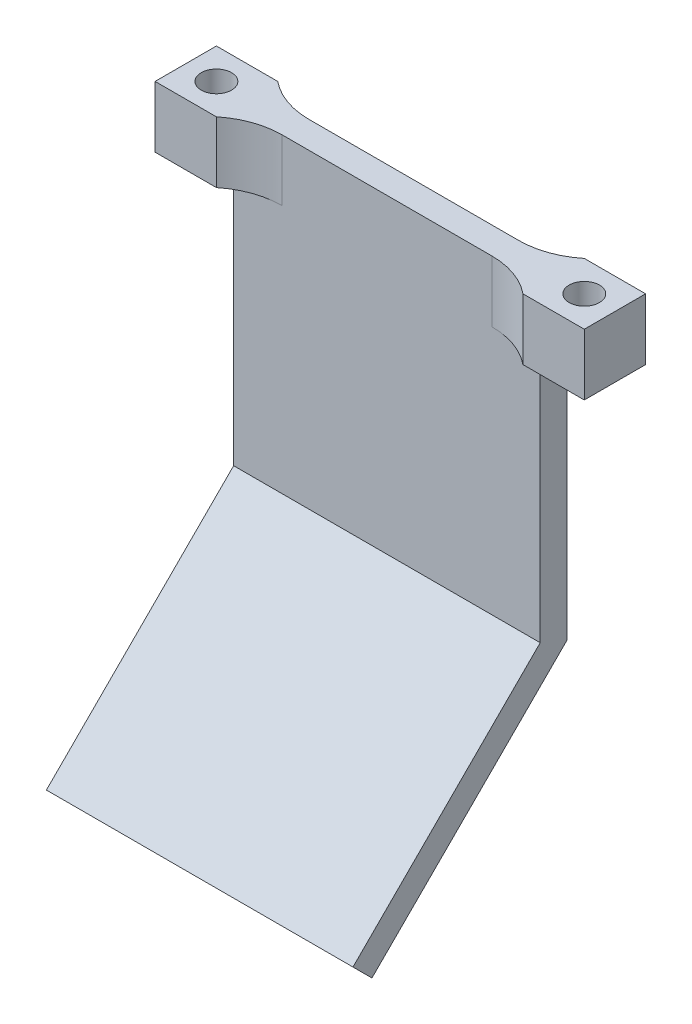
SolidWorks part; units mm, degrees
ref_plane "前视基准面" through (0, 0, 0) normal (0, 0, 1) x (1, 0, 0)
ref_plane "上视基准面" through (0, 0, 0) normal (0, 1, 0) x (1, 0, 0)
ref_plane "右视基准面" through (0, 0, 0) normal (1, 0, 0) x (0, 0, -1)
other "Configuration Table"
sketch "草图2" plane through (0, 0, 0) normal (1, 0, 0) x (0, 0, -1)
  line L0 (0, 0) -> (0, -42)
  line L1 (0, -42) -> (-25.4558, -67.4558)
  line L2 (-3.5, 0) -> (-3.5, -40.5503)
  line L3 (-3.5, -40.5503) -> (-27.9307, -64.981)
  line L4 (-3.5, 0) -> (0, 0)
  line L5 (-27.9307, -64.981) -> (-25.4558, -67.4558)
  point P3 (-3.5, -40.5503)
  dimension "D1" = 3.5
extrude "凸台-拉伸1" add sketch "草图2" along normal blind 40
sketch "草图3" plane through (0, 0, 3.5) normal (0, 0, 1) x (1, 0, 0)
  line L0 (40, -20.2751) -> (0, -20.2751)
  line L1 (40, 0) -> (40, -40.5503) construction
  line L2 (0, 0) -> (0, -40.5503) construction
  line L3 (20, -20.2751) -> (20, -4.2751)
  circle A0 centre (16, -4.2751) radius 1.5
  circle A1 centre (24, -4.2751) radius 1.5
  circle A2 centre (24, -36.2751) radius 1.5
  circle A3 centre (16, -36.2751) radius 1.5
sketch "草图4" plane through (0, 0, 0) normal (-1, 0, 0) x (0, 0, 1)
  line L5 (-2.25, 0) -> (5.75, 0)
  line L6 (-2.25, 0) -> (-2.25, -8)
  line L7 (-2.25, -8) -> (5.75, -8)
  line L8 (5.75, 0) -> (5.75, -8)
extrude "凸台-拉伸2" add sketch "草图4" along normal blind 8
sketch "草图5" plane through (0, 0, 0) normal (0, 1, 0) x (1, 0, 0)
  circle A0 centre (-4, -1.75) radius 1.98
extrude "切除-拉伸2" cut sketch "草图5" against normal blind 8
fillet "圆角1" radius 10 1 edges at (0, -4, 0)
fillet "圆角2" radius 10 1 edges at (0, -4, 3.5)
sketch "草图6" plane through (40, 0, 0) normal (1, 0, 0) x (0, 0, -1)
  line L1 (-5.75, 0) -> (2.25, 0)
  line L2 (-5.75, 0) -> (-5.75, -8)
  line L3 (-5.75, -8) -> (2.25, -8)
  line L4 (2.25, 0) -> (2.25, -8)
extrude "凸台-拉伸3" add sketch "草图6" along normal blind 8
sketch "草图7" plane through (0, 0, 0) normal (0, 1, 0) x (1, 0, 0)
  circle A0 centre (44, -1.75) radius 1.98
extrude "切除-拉伸3" cut sketch "草图7" against normal blind 8
fillet "圆角3" radius 10 1 edges at (40, -4, 0)
fillet "圆角4" radius 10 1 edges at (40, -4, 3.5)
sketch "草图8" plane through (0, 0, 0) normal (0, 0, -1) x (-1, 0, 0)
  circle A0 centre (-35, -21) radius 1.5
  circle A1 centre (-5, -21) radius 1.5
